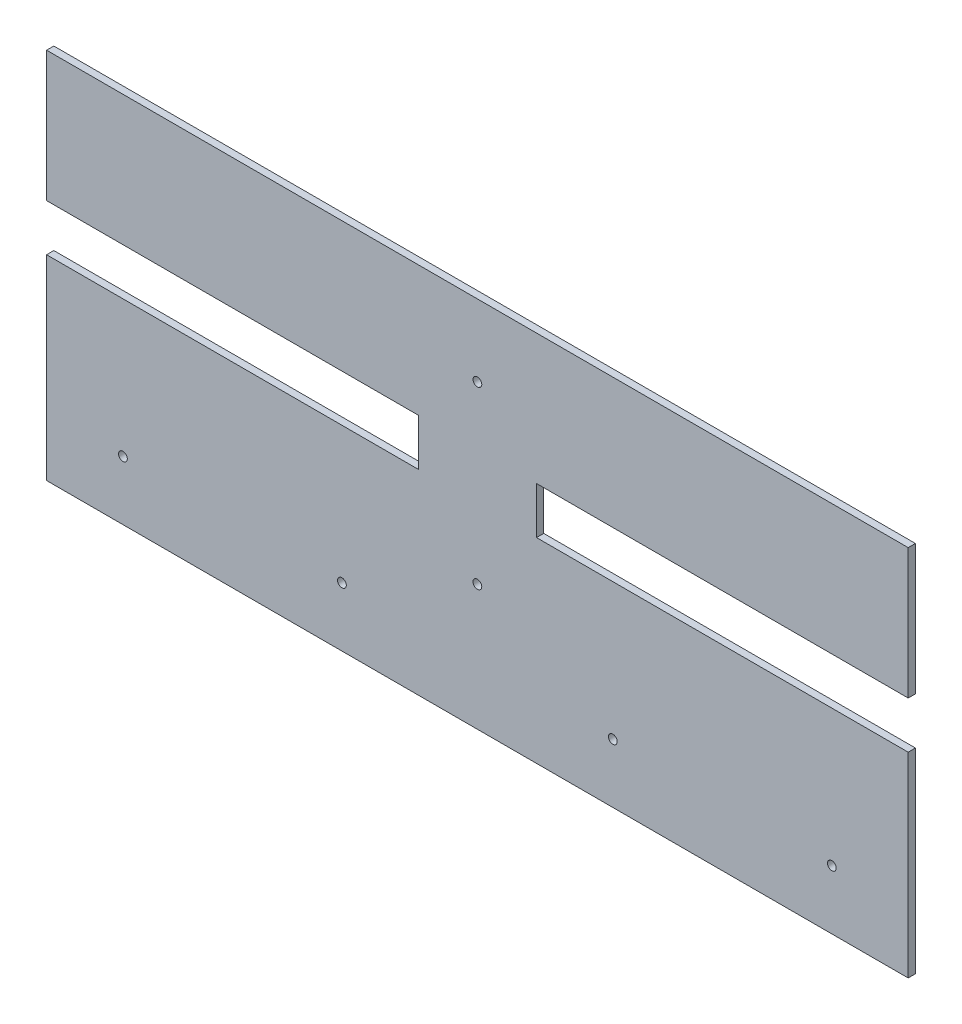
SolidWorks part; units mm, degrees
material "Balsa"
ref_plane "Front Plane" through (0, 0, 0) normal (0, 0, 1) x (1, 0, 0)
ref_plane "Top Plane" through (0, 0, 0) normal (0, 1, 0) x (1, 0, 0)
ref_plane "Right Plane" through (0, 0, 0) normal (1, 0, 0) x (0, 0, -1)
sketch "Sketch1" plane through (0, 0, 0) normal (0, 0, 1) x (1, 0, 0)
  line L1 (223.7, -24.5) -> (-169.7, -24.5)
  line L2 (223.7, -24.5) -> (223.7, 145.6824)
  line L3 (223.7, 145.6824) -> (-169.7, 145.6824)
  line L4 (-169.7, -24.5) -> (-169.7, 145.6824)
  line L5 (223.7, -24.5) -> (-169.7, 145.6824) construction
  line L6 (223.7, 145.6824) -> (-169.7, -24.5) construction
  line L7 (227, -24.5) -> (223.7, -24.5) construction
  line L9 (223.7, 145.6824) -> (54, 145.6824) construction
  line L10 (223.7, 144.1231) -> (223.7, -24.5) construction
  line L11 (-169.7, -24.5) -> (-169.7, 144.1269) construction
  point P4 (27, 60.5912)
extrude "Boss-Extrude1" add sketch "Sketch1" along normal up to surface (3.3 mm away)
sketch "Sketch2" plane through (0, 0, 0) normal (0, 0, -1) x (-1, 0, 0)
  line L0 (-223.7, 145.6824) -> (169.7, 145.6824) construction
  line L1 (0, 0) -> (-54, 0)
  line L2 (0, 0) -> (0, 145.6824)
  line L3 (0, 145.6824) -> (-54, 145.6824)
  line L4 (-54, 0) -> (-54, 145.6824)
  line L5 (0, 0) -> (-54, 145.6824) construction
  line L6 (0, 145.6824) -> (-54, 0) construction
  line L7 (-54, 262.7) -> (-54, 0) construction
  line L8 (-27, 0) -> (-27, 145.6824) construction
  line L9 (169.7, 145.6824) -> (169.7, -24.5) construction
  line L10 (-223.7, 29.5) -> (-54, 29.5)
  line L11 (-223.7, 29.5) -> (-223.7, -24.5)
  line L12 (-223.7, -24.5) -> (-54, -24.5)
  line L13 (-54, 29.5) -> (-54, -24.5)
  line L14 (-223.7, 29.5) -> (-54, -24.5) construction
  line L15 (-223.7, -24.5) -> (-54, 29.5) construction
  line L16 (169.7, 29.5) -> (0, 29.5)
  line L17 (169.7, 29.5) -> (169.7, -24.5)
  line L18 (169.7, -24.5) -> (0, -24.5)
  line L19 (0, 29.5) -> (0, -24.5)
  line L20 (169.7, 29.5) -> (0, -24.5) construction
  line L21 (169.7, -24.5) -> (0, 29.5) construction
  line L22 (-223.7, 2.5) -> (169.7, 2.5) construction
  line L23 (-138.85, -24.5) -> (-138.85, 29.5) construction
  circle A0 centre (-27, 32.8412) radius 2
  circle A1 centre (-27, 112.8412) radius 2
  circle A2 centre (-188.85, 2.5) radius 2
  circle A3 centre (-88.85, 2.5) radius 2
  circle A4 centre (34.85, 2.5) radius 2
  circle A5 centre (134.85, 2.5) radius 2
  point P4 (-27, 72.8412)
  point P20 (-138.85, 2.5)
  point P27 (84.85, 2.5)
  dimension "D1" = 4
  dimension "D2" = 4
  dimension "D3" = 40
  dimension "D4" = 40
  dimension "D5" = 4
  dimension "D6" = 50
extrude "Cut-Extrude1" cut sketch "Sketch2" against normal blind 4 contours A1 | A0 | A2 | A3 | A5 | A4
sketch "Sketch3" plane through (0, 0, 0) normal (0, 0, -1) x (-1, 0, 0)
  line L0 (169.7, 145.6824) -> (169.7, -24.5) construction
  line L1 (169.7, 64.8) -> (-223.7, 64.8)
  line L2 (169.7, 64.8) -> (169.7, 86.2)
  line L3 (169.7, 86.2) -> (-223.7, 86.2)
  line L4 (-223.7, 64.8) -> (-223.7, 86.2)
  line L5 (169.7, 64.8) -> (-223.7, 86.2) construction
  line L6 (169.7, 86.2) -> (-223.7, 64.8) construction
  line L7 (-223.7, -24.5) -> (-223.7, 145.6824) construction
  line L8 (35.8344, 64.8) -> (9.0983, 64.8) construction
  line L9 (142.922, 86.2) -> (163.7817, 86.2) construction
  line L10 (0, 64.8) -> (0, 86.2)
  line L11 (-54, 64.8) -> (-54, 86.2)
  line L12 (-54, 262.7) -> (-54, 0) construction
  line L13 (0, 262.7) -> (0, 0) construction
  line L14 (0, 262.7) -> (0, 0) construction
  point P4 (-27, 75.5)
  point P21 (0, 86.2)
  line M7 (-223.7, 145.6824) -> (-223.7, -24.5)
  line M9 (169.7, -24.5) -> (169.7, 145.6824)
extrude "Cut-Extrude2" cut sketch "Sketch3" against normal blind 6 contours L10 L1 L3 M9 | L1 L11 L3 M7 region at (-84.85, 75.5, 0) region at (138.85, 75.5, 0)
